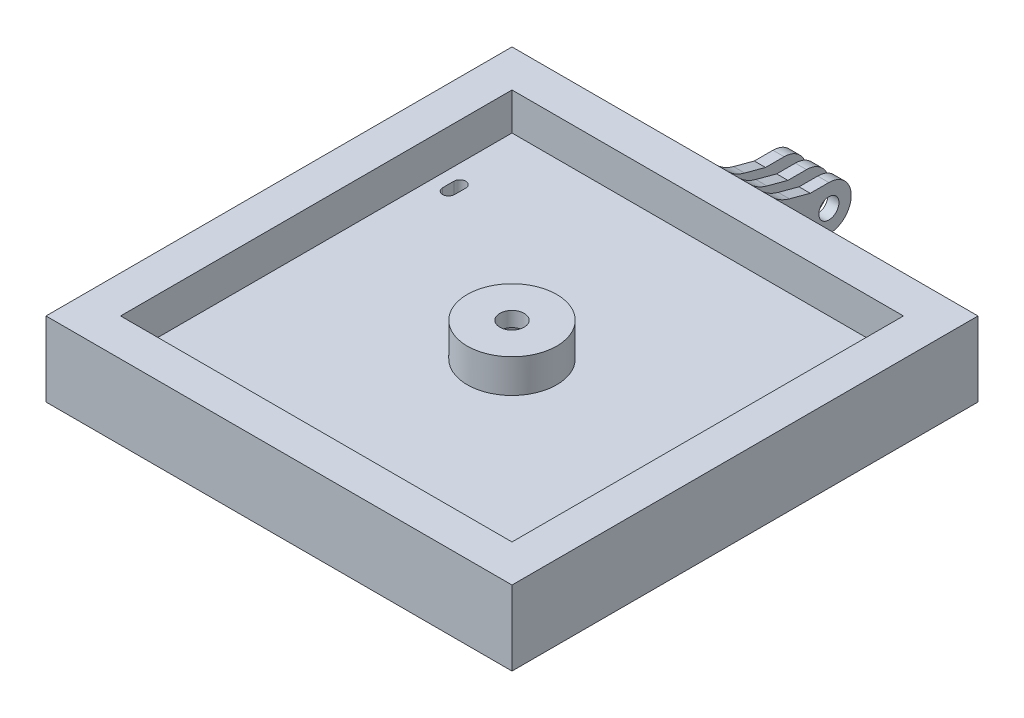
SolidWorks part; units mm, degrees
ref_plane "Front Plane" through (0, 0, 0) normal (0, 0, 1) x (1, 0, 0)
ref_plane "Top Plane" through (0, 0, 0) normal (0, 1, 0) x (1, 0, 0)
ref_plane "Right Plane" through (0, 0, 0) normal (1, 0, 0) x (0, 0, -1)
sketch "Sketch1" plane through (0, 0, 0) normal (0, 1, 0) x (1, 0, 0)
  line L0 (-62.5, 62.5) -> (62.5, 62.5)
  line L1 (-52.5, 52.5) -> (52.5, 52.5)
  line L2 (-52.5, 52.5) -> (-52.5, -52.5)
  line L3 (-52.5, -52.5) -> (52.5, -52.5)
  line L4 (52.5, 52.5) -> (52.5, -52.5)
  line L5 (-52.5, 52.5) -> (52.5, -52.5) construction
  line L6 (-52.5, -52.5) -> (52.5, 52.5) construction
  line L7 (62.5, 62.5) -> (62.5, -62.5)
  line L8 (-62.5, -62.5) -> (62.5, -62.5)
  line L9 (-62.5, 62.5) -> (-62.5, -62.5)
  point P0 (0, 0)
  dimension "D1" = 105
  dimension "D2" = 105
  dimension "D3" = 10
extrude "Boss-Extrude1" add sketch "Sketch1" along normal blind 10
sketch "Sketch2" plane through (0, 0, 0) normal (0, -1, 0) x (1, 0, 0)
  line L1 (-62.5, 62.5) -> (62.5, 62.5)
  line L2 (-62.5, 62.5) -> (-62.5, -62.5)
  line L3 (-62.5, -62.5) -> (62.5, -62.5)
  line L4 (62.5, 62.5) -> (62.5, -62.5)
  line L5 (-62.5, 62.5) -> (62.5, -62.5) construction
  line L6 (-62.5, -62.5) -> (62.5, 62.5) construction
  point P0 (0, 0)
extrude "Boss-Extrude2" add sketch "Sketch2" along normal blind 10
sketch "Sketch3" plane through (0, 0, 0) normal (0, 1, 0) x (1, 0, 0)
  line L0 (-47.5, 33.5) -> (-47.5, 30.5) construction
  line L1 (-45.9, 33.5) -> (-45.9, 30.5)
  line L2 (-49.1, 33.5) -> (-49.1, 30.5)
  line L3 (-47.5, -46.5) -> (-47.5, -49.5) construction
  line L4 (-45.9, -46.5) -> (-45.9, -49.5)
  line L5 (-49.1, -46.5) -> (-49.1, -49.5)
  line L6 (-52.5, -52.5) -> (52.5, -52.5) construction
  line L7 (-52.5, 52.5) -> (-52.5, -52.5) construction
  arc A0 (-45.9, 33.5) -> (-49.1, 33.5) centre (-47.5, 33.5) ccw
  arc A1 (-49.1, 30.5) -> (-45.9, 30.5) centre (-47.5, 30.5) ccw
  arc A2 (-45.9, -46.5) -> (-49.1, -46.5) centre (-47.5, -46.5) ccw
  arc A3 (-49.1, -49.5) -> (-45.9, -49.5) centre (-47.5, -49.5) ccw
  point P2 (-47.5, 32)
  point P7 (-47.5, -48)
  dimension "D1" = 1.6
  dimension "D2" = 4.5
  dimension "D3" = 3
  dimension "D4" = 80
  dimension "D5" = 5
extrude "Cut-Extrude1" cut sketch "Sketch3" against normal blind 10
sketch "Sketch4" plane through (0, -10, 0) normal (0, -1, 0) x (1, 0, 0)
  line L0 (-47.5, 49.5) -> (-47.5, 46.5) construction
  line L1 (-43.5, 49.5) -> (-43.5, 46.5)
  line L2 (-51.5, 49.5) -> (-51.5, 46.5)
  line L3 (-47.5, -30.5) -> (-47.5, -33.5) construction
  line L4 (-43.5, -30.5) -> (-43.5, -33.5)
  line L5 (-51.5, -30.5) -> (-51.5, -33.5)
  arc A0 (-43.5, 49.5) -> (-51.5, 49.5) centre (-47.5, 49.5) ccw
  arc A1 (-51.5, 46.5) -> (-43.5, 46.5) centre (-47.5, 46.5) ccw
  arc A2 (-43.5, -30.5) -> (-51.5, -30.5) centre (-47.5, -30.5) ccw
  arc A3 (-51.5, -33.5) -> (-43.5, -33.5) centre (-47.5, -33.5) ccw
  point P4 (-47.5, 48)
  point P13 (-47.5, -32)
  dimension "D1" = 4
extrude "Cut-Extrude2" cut sketch "Sketch4" against normal blind 5
mirror "Mirror1" about plane through (0, 0, 0) normal (1, 0, 0) of "Cut-Extrude2", "Cut-Extrude1"
sketch "Sketch5" plane through (0, 0, 0) normal (1, 0, 0) x (0, 0, -1)
  line L0 (62.5, 10) -> (62.5, -10) construction
  line L1 (62.5, 6) -> (77.5, 6)
  line L2 (62.5, 6) -> (62.5, -6)
  line L3 (62.5, -6) -> (77.5, -6)
  line L5 (55, 0) -> (-55, 0) construction
  arc A0 (77.5, 6) -> (77.5, -6) centre (77.5, 0) cw
  point P7 (62.5, 0)
  dimension "D1" = 6
  dimension "D2" = 15
extrude "Boss-Extrude4" add sketch "Sketch5" along normal mid plane 3
pattern_linear "LPattern3" count 2 spacing 6 along (1, 0, 0) count 2 spacing 6 along (-1, 0, 0) of "Boss-Extrude4"
chamfer "Chamfer1" distance 10 angle 15 6 edges at (0, 6, -62.5) (0, -6, -62.5) (6, 6, -62.5) (-6, 6, -62.5) (6, -6, -62.5) (-6, -6, -62.5) first distance on face at (0, 6, -70) first distance on face at (0, -6, -70) first distance on face at (6, 6, -70) first distance on face at (-6, 6, -70) first distance on face at (6, -6, -70) first distance on face at (-6, -6, -70)
fillet "Fillet1" radius 10 6 edges at (0, 8.6795, -62.5) (0, -8.6795, -62.5) (6, -8.6795, -62.5) (-6, -8.6795, -62.5) (6, 8.6795, -62.5) (-6, 8.6795, -62.5)
sketch "Sketch6" plane through (-7.5, 0, 0) normal (-1, 0, 0) x (0, 0, 1)
  circle A0 centre (-77.5, 0) radius 2.7
  dimension "D1" = 5.4
extrude "Cut-Extrude3" cut sketch "Sketch6" against normal through all
sketch "Sketch7" plane through (0, 0, 0) normal (0, 1, 0) x (1, 0, 0)
  line L1 (8.5, 0) -> (4.25, 7.3612)
  line L2 (4.25, 7.3612) -> (-4.25, 7.3612)
  line L3 (-4.25, 7.3612) -> (-8.5, 0)
  line L4 (-8.5, 0) -> (-4.25, -7.3612)
  line L5 (-4.25, -7.3612) -> (4.25, -7.3612)
  line L6 (4.25, -7.3612) -> (8.5, 0)
  circle A0 centre (0, 0) radius 8.5 construction
  dimension "D1" = 17
extrude "Cut-Extrude4" cut sketch "Sketch7" against normal blind 10
sketch "Sketch8" plane through (0, 0, 0) normal (0, 1, 0) x (1, 0, 0)
  line L1 (8.5, 0) -> (4.25, 7.3612)
  line L2 (4.25, 7.3612) -> (-4.25, 7.3612)
  line L3 (-4.25, 7.3612) -> (-8.5, 0)
  line L4 (-8.5, 0) -> (-4.25, -7.3612)
  line L5 (-4.25, -7.3612) -> (4.25, -7.3612)
  line L6 (4.25, -7.3612) -> (8.5, 0)
  circle A0 centre (0, 0) radius 7.3612 construction
  circle A1 centre (0, 0) radius 12
extrude "Boss-Extrude5" add sketch "Sketch8" along normal blind 5
sketch "Sketch9" plane through (0, 5, 0) normal (0, 1, 0) x (1, 0, 0)
  circle A0 centre (0, 0) radius 12
  circle A1 centre (0, 0) radius 3.25
extrude "Boss-Extrude6" add sketch "Sketch9" along normal blind 4
equation "\"q\"=15"
